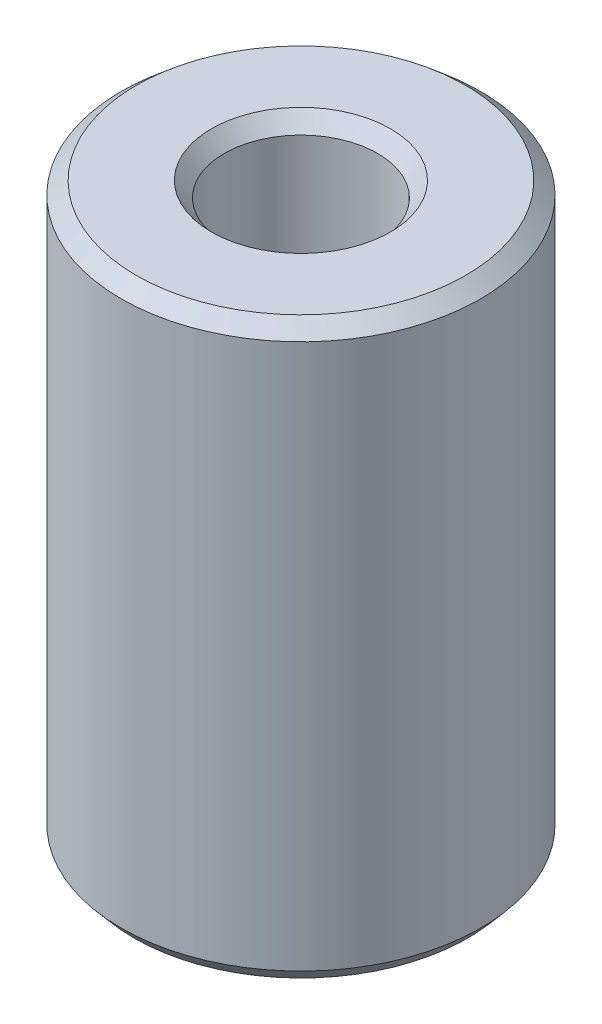
SolidWorks part; units mm, degrees
ref_plane "Front Plane" through (0, 0, 0) normal (0, 0, 1) x (1, 0, 0)
ref_plane "Top Plane" through (0, 0, 0) normal (0, 1, 0) x (1, 0, 0)
ref_plane "Right Plane" through (0, 0, 0) normal (1, 0, 0) x (0, 0, -1)
sketch "Sketch1" plane through (0, 0, 0) normal (0, 1, 0) x (1, 0, 0)
  circle A0 centre (0, 0) radius 42.5
  dimension "SLEEVE_OD" = 85
extrude "Boss-Extrude1" add sketch "Sketch1" along normal blind 135.4743
sketch "Sketch2" plane through (0, 0, 0) normal (0, 1, 0) x (1, 0, 0)
  circle A0 centre (0, 0) radius 18.1518
  dimension "BORE_D" = 36.3036
extrude "Cut-Extrude1" cut sketch "Sketch2" along normal through all
chamfer "Chamfer1" distance 3.0208 angle 49.624 4 edges at (0, 135.4743, 18.1518) (0, 0, 18.1518) (0, 0, 42.5) (0, 135.4743, 42.5) first distance on face at (0, 135.4743, 18.1518) first distance on face at (0, 0, 18.1518) first distance on face at (0, 135.4743, 42.5)
